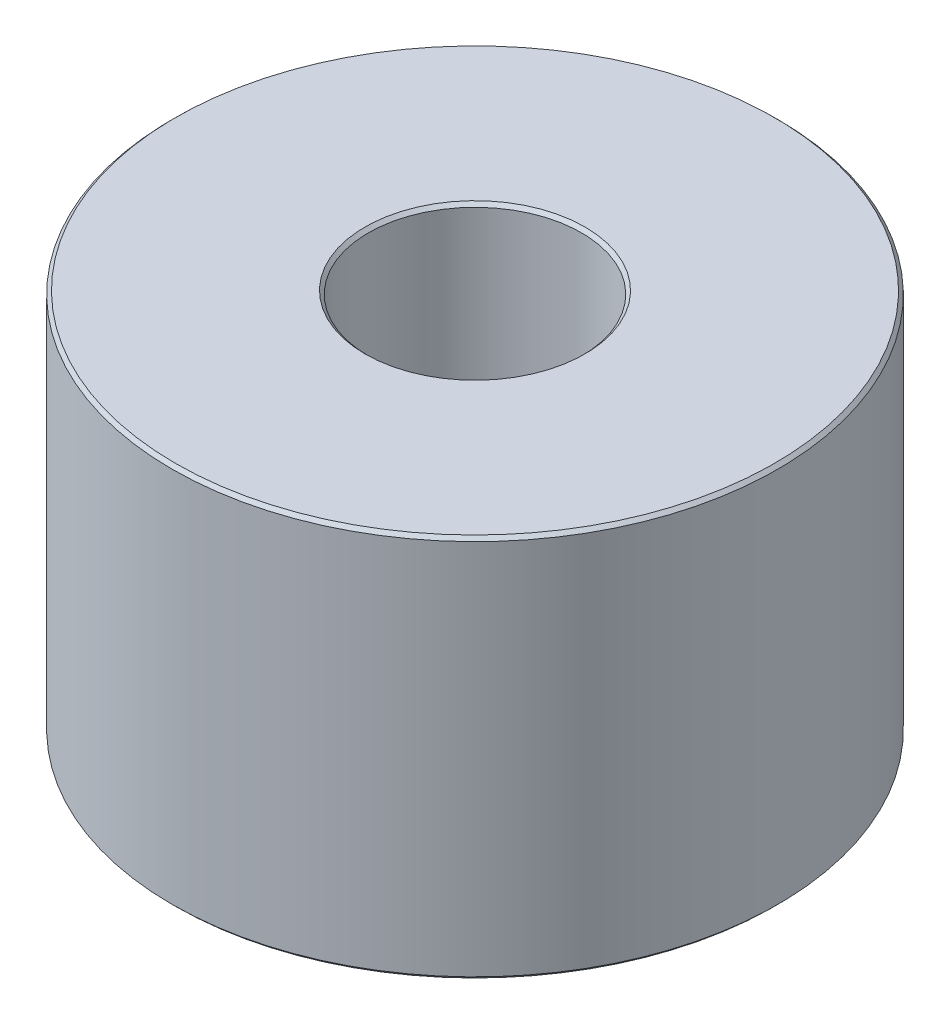
SolidWorks part; units mm, degrees
material "6061 Alloy"
ref_plane "Front Plane" through (0, 0, 0) normal (0, 0, 1) x (1, 0, 0)
ref_plane "Top Plane" through (0, 0, 0) normal (0, 1, 0) x (1, 0, 0)
ref_plane "Right Plane" through (0, 0, 0) normal (1, 0, 0) x (0, 0, -1)
sketch "main_dimensions_sketch" plane through (0, 0, 0) normal (0, 1, 0) x (1, 0, 0)
  circle A0 centre (0, 0) radius 5.5
  circle A1 centre (0, 0) radius 9
  circle A2 centre (0, 0) radius 3.1686
  dimension "D1" = 11
  dimension "D2" = 18
  dimension "D3" = 6.3373
extrude "body" add sketch "main_dimensions_sketch" along normal blind 10 contours A1 A0 | A0 A2 region at (-5.3444, 0, 0) region at (-8.7454, 0, 0)
extrude "lip" add sketch "Sketch1<3>" against normal blind 1.4 contours A1 A0 region at (-8.7454, 0, 0)
sketch "Sketch1<3>" plane through (0, 0, 0) normal (0, 1, 0) x (1, 0, 0) same geometry as "main_dimensions_sketch"
chamfer "break_edges" distance 0.1 angle 45 5 edges at (0, -1.4, 9) (0, -1.4, 5.5) (0, 10, 3.1686) (0, 10, 9) (0, 0, 3.1686)
